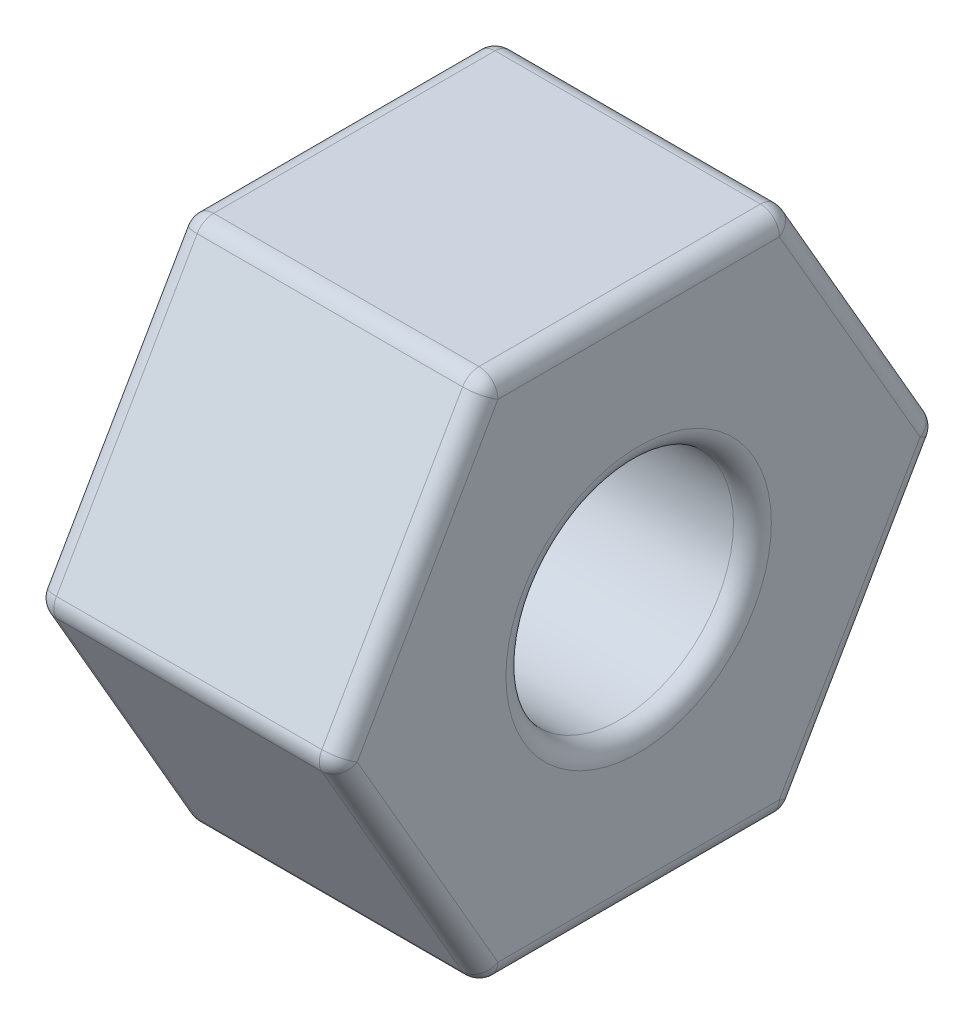
SolidWorks part; units mm, degrees
material "AISI 4140 Steel, quenched & tempered"
ref_plane "Front Plane" through (0, 0, 0) normal (1, 0, 0) x (0, 1, 0)
ref_plane "Top Plane" through (0, 0, 0) normal (0, 0, 1) x (0, 1, 0)
ref_plane "Right Plane" through (0, 0, 0) normal (0, 1, 0) x (-1, 0, 0)
sketch "Sketch1" plane through (0, 0, 0) normal (1, 0, 0) x (0, 1, 0)
  line L0 (-12.0894, 0) -> (9.8859, 0) construction
  line L1 (-6.9282, -4) -> (0, -8)
  line L2 (0, -8) -> (6.9282, -4)
  line L3 (6.9282, -4) -> (6.9282, 4)
  line L4 (6.9282, 4) -> (0, 8)
  line L5 (0, 8) -> (-6.9282, 4)
  line L6 (-6.9282, 4) -> (-6.9282, -4)
  line L7 (0, 9.3408) -> (0, -11.217) construction
  circle A0 centre (0, 0) radius 6.9282 construction
  circle A1 centre (0, 0) radius 3
  point P11 (-6.9282, 0)
  point P12 (6.9282, 0)
  dimension "D2" = 6
  dimension "D1" = 8
extrude "Boss-Extrude1" add sketch "Sketch1" along normal blind 8
fillet "Fillet1" radius 0.5 20 edges at (0, 0, -3) (8, 0, -3) (0, -6.9282, 0) (0, -3.4641, -6) (0, 3.4641, -6) (0, 6.9282, 0) (0, 3.4641, 6) (0, -3.4641, 6) (8, -6.9282, 0) (8, -3.4641, -6) (8, 3.4641, -6) (8, 6.9282, 0) (8, 3.4641, 6) (8, -3.4641, 6) (4, -6.9282, 4) (4, 0, 8) (4, 6.9282, -4) (4, 0, -8) (4, -6.9282, -4) (4, 6.9282, 4)
ref_axis "Axis1" through (7.5, 0, 0) along (-1, 0, 0)
